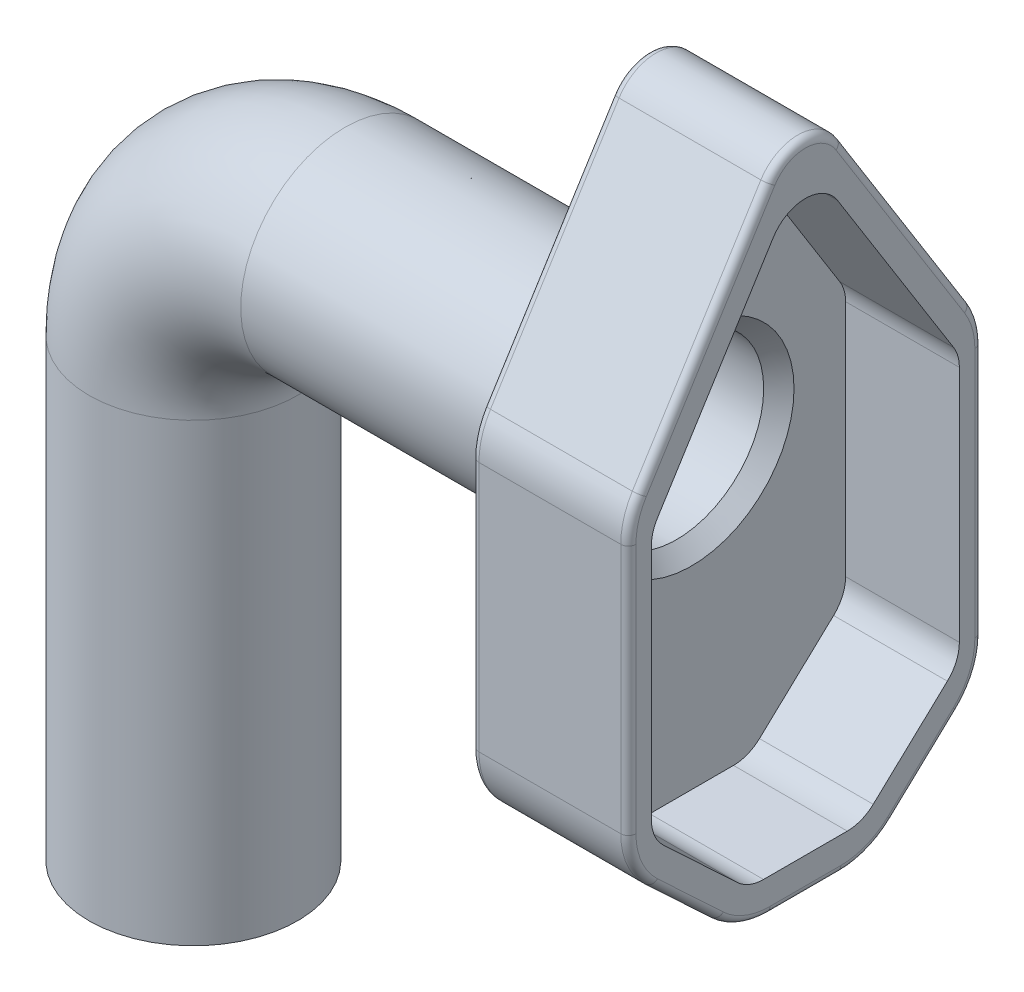
SolidWorks part; units mm, degrees
ref_plane "Front Plane" through (0, 0, 0) normal (1, 0, 0) x (0, 1, 0)
ref_plane "Top Plane" through (0, 0, 0) normal (0, 0, 1) x (0, 1, 0)
ref_plane "Right Plane" through (0, 0, 0) normal (0, 1, 0) x (-1, 0, 0)
sketch "Sketch1" plane through (0, 0, 0) normal (1, 0, 0) x (0, 1, 0)
  line L0 (0, 0) -> (25.6534, -16.0621)
  line L1 (0, 0) -> (-35, 0)
  line L2 (0, 0) -> (0, -40.6)
  line L3 (0, -40.6) -> (-35, -40.6)
  line L4 (-35, 0) -> (-35, -40.6)
  line L5 (25.6534, -24.5379) -> (0, -40.6)
  line L6 (-35, 0) -> (-47, -12.8)
  line L7 (-47, -12.8) -> (-47, -27.8)
  line L8 (-47, -27.8) -> (-35, -40.6)
  arc A0 (25.6534, -24.5379) -> (25.6534, -16.0621) centre (23, -20.3) ccw
  point P5 (-47, -20.3)
  point P7 (0, -20.3)
  point P10 (32.4218, -20.3)
  point P13 (-35, -20.3)
  point P14 (28, -20.3)
  dimension "D2" = 5
  dimension "D6" = 28
  dimension "D1" = 40.6
  dimension "D3" = 15
  dimension "D4" = 75
  dimension "D5" = 35
extrude "Boss-Extrude1" add sketch "Sketch1" along normal blind 18 contours L1 L4 L3 L2 | L7 L8 L4 L6 | L5 A0 L0 L2 region at (0, -17.5, -20.3) region at (0, 10.3898, -20.3) region at (0, -40.0791, -20.3)
scale "Scale1" scale about centroid uniform scaling yes scale factor 1.15
sketch "Sketch7" plane through (19.35, 0, 0) normal (1, 0, 0) x (0, 1, 0)
  line L0 (-0.5765, 0) -> (25.0769, -16.0621)
  line L1 (-0.5765, 0) -> (-35.5765, 0)
  line L2 (-0.5765, 0) -> (-0.5765, -40.6)
  line L3 (-0.5765, -40.6) -> (-35.5765, -40.6)
  line L4 (-35.5765, 0) -> (-35.5765, -40.6)
  line L5 (25.0769, -24.5379) -> (-0.5765, -40.6)
  line L6 (-35.5765, 0) -> (-47.5765, -12.8)
  line L7 (-47.5765, -12.8) -> (-47.5765, -27.8)
  line L8 (-47.5765, -27.8) -> (-35.5765, -40.6)
  line L9 (1.9735, 3.045) -> (-38.2765, 3.045) construction
  line L10 (-52.0765, -11.675) -> (-52.0765, -28.925) construction
  arc A0 (25.0769, -24.5379) -> (25.0769, -16.0621) centre (22.4235, -20.3) ccw
  arc A1 (31.475, -25.1735) -> (31.475, -15.4265) centre (28.4235, -20.3) ccw construction
  point P4 (-47.5765, -20.3)
  point P6 (-0.5765, -20.3)
  point P11 (-35.5765, -20.3)
  point P12 (27.4235, -20.3)
  point P17 (-52.0765, -20.3)
  point P21 (34.1735, -20.3)
  dimension "D2" = 5
  dimension "D1" = 40.6
  dimension "D3" = 15
  dimension "D4" = 75
  dimension "D5" = 35
  dimension "D6" = 28
  dimension "D7" = 4.5
extrude "Cut-Extrude1" cut sketch "Sketch7" against normal blind 15 contours L1 L4 L3 L2 | L7 L8 L4 L6 | L5 A0 L0 L2 region at (19.35, -18.0765, -20.3) region at (19.35, 9.8134, -20.3) region at (19.35, -40.6556, -20.3)
fillet "Fillet1" radius 10 6 edges at (9, 1.9735, 3.045) (9, -38.2765, 3.045) (9, -52.0765, -11.675) (9, -52.0765, -28.925) (9, 1.9735, -43.645) (9, -38.2765, -43.645)
fillet "Fillet2" radius 5 6 edges at (11.85, -0.5765, -40.6) (11.85, -35.5765, -40.6) (11.85, -47.5765, -27.8) (11.85, -47.5765, -12.8) (11.85, -0.5765, 0) (11.85, -35.5765, 0)
fillet "Fillet3" radius 1 14 edges at (19.35, -45.3057, -36.1472) (19.35, -51.3758, -28.6479) (19.35, -52.0765, -20.3) (19.35, -51.3758, -11.9521) (19.35, -45.3057, -4.4528) (19.35, -37.9194, 2.2209) (19.35, -17.4215, 3.045) (19.35, 1.8619, 2.6564) (19.35, 17.9415, -6.9529) (19.35, 34.1735, -20.3) (19.35, 17.9415, -33.6471) (19.35, 1.8619, -43.2564) (19.35, -17.4215, -43.645) (19.35, -37.9194, -42.8209)
fillet "Fillet4" radius 1 14 edges at (-1.35, 1.8619, -43.2564) (-1.35, 17.9415, -33.6471) (-1.35, 34.1735, -20.3) (-1.35, 17.9415, -6.9529) (-1.35, 1.8619, 2.6564) (-1.35, -17.4215, 3.045) (-1.35, -37.9194, 2.2209) (-1.35, -45.3057, -4.4528) (-1.35, -51.3758, -11.9521) (-1.35, -52.0765, -20.3) (-1.35, -51.3758, -28.6479) (-1.35, -45.3057, -36.1472) (-1.35, -37.9194, -42.8209) (-1.35, -17.4215, -43.645)
sketch "Sketch9" plane through (-1.35, 0, 0) normal (-1, 0, 0) x (0, -1, 0)
  line L0 (0.8988, 2.045) -> (0.8988, -43.645) construction
  line L1 (51.0765, -24.9705) -> (51.0765, -15.6295) construction
  circle A0 centre (8.5434, -20.3) radius 11.5
  point P8 (51.0765, -20.3)
  point P9 (0, 0)
  dimension "D1" = 23
extrude "Cut-Extrude2" cut sketch "Sketch9" against normal through all
chamfer "Chamfer1" distance 2 angle 45 1 edges at (4.35, -8.5434, -31.8)
sketch "Sketch10" plane through (0, -52.0765, 0) normal (0, -1, 0) x (1, 0, 0)
  line L0 (-1.35, -20.3) -> (19.35, -20.3) construction
  line L1 (-1.35, -8.8) -> (-1.35, -31.8) construction
  line L2 (19.35, -15.6295) -> (19.35, -24.9705) construction
ref_plane "Plane1" through (0, 0, -20.3) normal (0, 0, 1) x (1, 0, 0)
sketch "Sketch11" plane through (0, 0, -20.3) normal (0, 0, 1) x (1, 0, 0)
  line L0 (-1.35, -8.5434) -> (-41.35, -8.5434)
  line L1 (-61.35, -28.5434) -> (-61.35, -88.5434)
  arc A0 (-41.35, -8.5434) -> (-61.35, -28.5434) centre (-41.35, -28.5434) ccw
  dimension "D1" = 20
  dimension "D2" = 40
  dimension "D3" = 60
sweep "Sweep1" add path "Sketch11" circular profile diameter 27.5 parameters "D3"=27.5
sweep "Cut-Sweep2" cut path "Sketch11<3>" circular profile diameter 23 parameters "D3"=23
sketch "Sketch11<3>" plane through (0, 0, -20.3) normal (0, 0, 1) x (1, 0, 0) same geometry as "Sketch11"
sketch "Sketch13" plane through (0, -88.5434, 0) normal (0, -1, 0) x (1, 0, 0)
  line L0 (-61.35, -20.3) -> (-61.35, -52.718) construction
  line L1 (-63.7382, -26.6007) -> (-58.9618, -26.6007)
  line L2 (-63.7382, -26.6007) -> (-63.7382, -32.0884)
  line L3 (-63.7382, -32.0884) -> (-58.9618, -32.0884)
  line L4 (-58.9618, -26.6007) -> (-58.9618, -32.0884)
  point P8 (-61.35, -26.6007)
extrude "Cut-Extrude3" cut sketch "Sketch13" against normal blind 10
sketch "Sketch14" plane through (-63.7382, 0, 0) normal (1, 0, 0) x (0, 1, 0)
  line L1 (-78.5434, -28.0178) -> (-91.1068, -28.0178)
  line L2 (-78.5434, -28.0178) -> (-78.5434, -32.0884)
  line L3 (-78.5434, -32.0884) -> (-91.1068, -32.0884)
  line L4 (-78.5434, -31.5493) -> (-88.5434, -31.5493)
  line L5 (-88.5434, -31.5493) -> (-88.5434, -32.0884)
  line L6 (-88.5434, -32.0884) -> (-78.5434, -32.0884)
  line L7 (-78.5434, -32.0884) -> (-78.5434, -31.5493)
  line L8 (-78.5434, -28.0178) -> (-91.1068, -28.0178)
  line L9 (-88.5434, -31.5493) -> (-88.5434, -32.0884)
  line L10 (-91.1068, -32.0884) -> (-78.5434, -32.0884)
  line L11 (-78.5434, -32.0884) -> (-78.5434, -28.0178)
  line L12 (-91.1068, -28.0178) -> (-91.1068, -32.0884)
  point P7 (0, 0)
  point P8 (0, 0)
  dimension "D1" = 0
sketch "Sketch16" plane through (-63.7382, 0, 0) normal (1, 0, 0) x (0, 1, 0)
  line L0 (-91.1068, -28.0178) -> (-91.1068, -32.0884) construction
  line L1 (-78.5434, -32.0884) -> (-91.1068, -32.0884) construction
  line L2 (-78.5434, -28.0178) -> (-78.5434, -32.0884) construction
  line L3 (-78.5434, -28.0178) -> (-91.1068, -28.0178) construction
  line L4 (-91.1068, -28.0178) -> (-91.1068, -32.0884)
  line L5 (-78.5434, -32.0884) -> (-91.1068, -32.0884)
  line L6 (-78.5434, -28.0178) -> (-78.5434, -32.0884)
  line L7 (-78.5434, -28.0178) -> (-91.1068, -28.0178)
extrude "Cut-Extrude5" cut sketch "Sketch16" against normal blind 3
